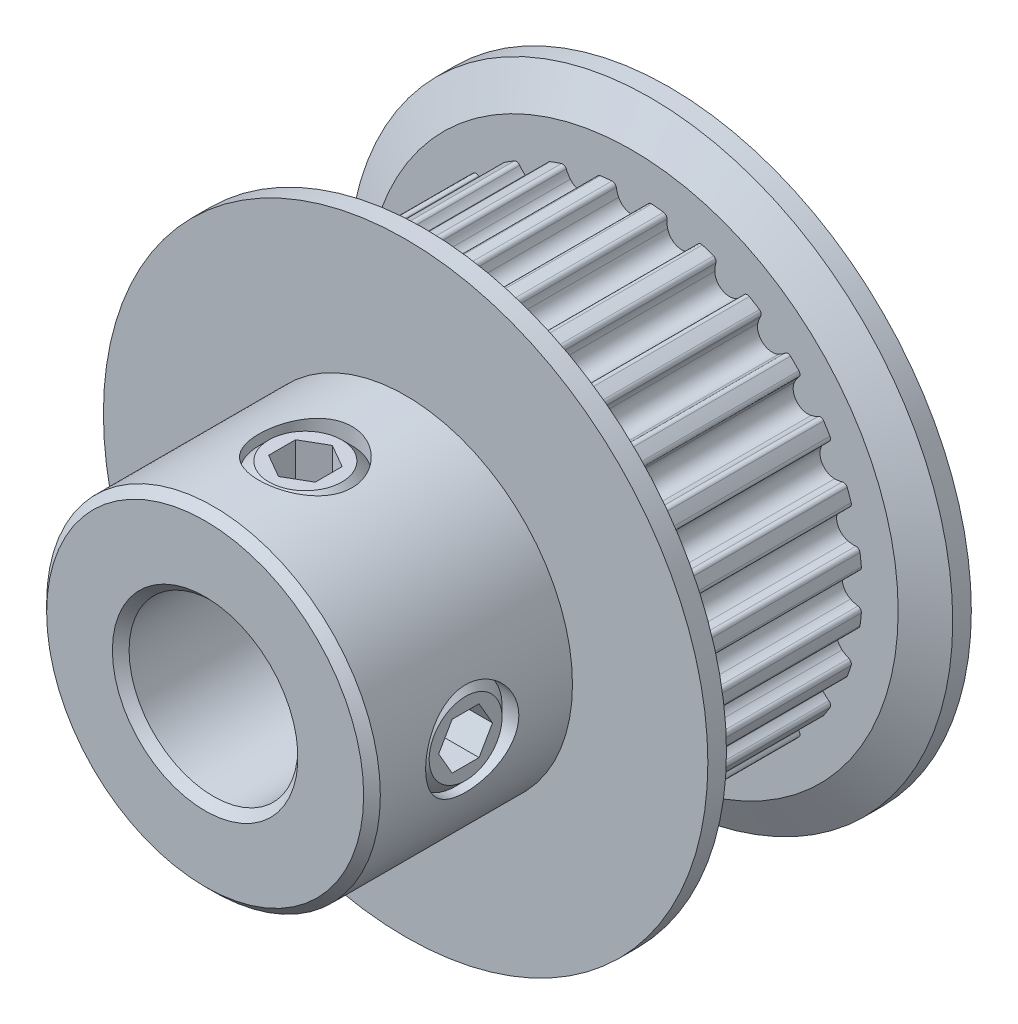
SolidWorks part; units mm, degrees
ref_plane "Front Plane" through (0, 0, 0) normal (0, 0, 1) x (1, 0, 0)
ref_plane "Top Plane" through (0, 0, 0) normal (0, 1, 0) x (1, 0, 0)
ref_plane "Right Plane" through (0, 0, 0) normal (1, 0, 0) x (0, 0, -1)
sketch "Sketch1" plane through (0, 0, 0) normal (0, 0, 1) x (1, 0, 0)
  line L1 (-1.8091, 7.9115) -> (1.8091, 7.9115) construction
  line L4 (0, 0) -> (0, 7.9115) construction
  line L5 (0, 7.9115) -> (0, 12.1188) construction
  line L6 (0, 8.9155) -> (1.9874, 8.6912) construction
  line L7 (1.9874, 8.6912) -> (2.7671, 8.5129) construction
  line L8 (1.9874, 8.6912) -> (1.8091, 7.9115) construction
  line L9 (-1.9874, 8.6912) -> (-1.8091, 7.9115) construction
  line L10 (-1.9308, 8.4436) -> (-2.5991, 11.3665)
  line L11 (-2.5991, 11.3665) -> (2.5991, 11.3665)
  line L12 (2.5991, 11.3665) -> (1.9308, 8.4436)
  circle A0 centre (0, 0) radius 8.9155 construction
  circle A1 centre (0, 0) radius 11.3665 construction
  circle A2 centre (0, 0) radius 8.6615 construction
  arc A3 (-0.4989, 8.2233) -> (0.4989, 8.2233) centre (0, 8.4665) ccw
  arc A4 (-0.4989, 8.2233) -> (-0.5874, 8.5034) centre (0.4, 8.6615) cw
  arc A5 (-1.9308, 8.4436) -> (-0.7485, 8.6291) centre (0, 0) cw
  arc A6 (-0.5874, 8.5034) -> (-0.7485, 8.6291) centre (-0.7355, 8.4797) ccw
  arc A7 (1.9308, 8.4436) -> (0.7485, 8.6291) centre (0, 0) ccw
  arc A8 (0.5874, 8.5034) -> (0.7485, 8.6291) centre (0.7355, 8.4797) cw
  arc A9 (0.4989, 8.2233) -> (0.5874, 8.5034) centre (-0.4, 8.6615) ccw
  point P6 (0, 20.9083)
  point P11 (0, 8.9155)
  point P13 (0, 11.3665)
  point P14 (0, 8.6615)
  dimension "D1" = 8.7896
  dimension "D2" = 3.2033
sketch "Sketch2" plane through (0, 0, 0) normal (1, 0, 0) x (0, 0, -1)
  line L0 (-8.7249, 3.175) -> (8.7249, 3.175)
  line L1 (-8.7249, 3.175) -> (-8.7249, 6.275)
  line L2 (-8.7249, 6.275) -> (-1.1851, 6.275)
  line L3 (-1.1851, 6.275) -> (-1.1851, 11.3665)
  line L4 (-1.1851, 11.3665) -> (0.2149, 11.3665) construction
  line L5 (0.2149, 11.3665) -> (0.2149, 8.6615) construction
  line L6 (0.2149, 8.6615) -> (7.3249, 8.6615)
  line L7 (7.3249, 8.6615) -> (7.3249, 11.3665) construction
  line L8 (7.3249, 11.3665) -> (8.7249, 11.3665) construction
  line L9 (8.7249, 11.3665) -> (8.7249, 3.175)
  line L10 (-8.7249, 0) -> (8.7249, 0) construction
  line L11 (8.0249, 11.3665) -> (7.3249, 10.014)
  line L12 (0.2149, 10.014) -> (-0.4851, 11.3665)
  line L13 (-1.1851, 11.3665) -> (-0.4851, 11.3665)
  line L14 (0.2149, 10.014) -> (0.2149, 8.6615)
  line L15 (7.3249, 8.6615) -> (7.3249, 10.014)
  line L16 (8.0249, 11.3665) -> (8.7249, 11.3665)
  arc A0 (0.2149, 10.014) -> (-0.4851, 11.3665) centre (-1.4417, 10.014) ccw construction
  arc A1 (7.3249, 10.014) -> (8.0249, 11.3665) centre (8.9815, 10.014) cw construction
  point P12 (0.2149, 10.014)
  point P14 (-0.4851, 11.3665)
  point P20 (7.3249, 10.014)
  point P21 (8.0249, 11.3665)
  point P25 (7.3249, 0)
  point P26 (0.2149, 0)
revolve "Revolve1" add sketch "Sketch2" angle 360 mid plane about L10
sketch "Sketch3" plane through (0, 0, 0) normal (0, 0, 1) x (1, 0, 0)
  line L6 (2.5991, 11.3665) -> (-2.5991, 11.3665)
  line L7 (1.9308, 8.4436) -> (2.5991, 11.3665)
  line L8 (-2.5991, 11.3665) -> (-1.9308, 8.4436)
  line L9 (2.5991, 11.3665) -> (-2.5991, 11.3665)
  line L10 (1.9308, 8.4436) -> (2.5991, 11.3665)
  line L11 (-2.5991, 11.3665) -> (-1.9308, 8.4436)
  arc A8 (1.9308, 8.4436) -> (0.7485, 8.6291) centre (0, 0) ccw
  arc A9 (0.7485, 8.6291) -> (0.5874, 8.5034) centre (0.7355, 8.4797) ccw
  arc A10 (0.4989, 8.2233) -> (0.5874, 8.5034) centre (-0.4, 8.6615) ccw
  arc A11 (-0.4989, 8.2233) -> (0.4989, 8.2233) centre (0, 8.4665) ccw
  arc A12 (-0.5874, 8.5034) -> (-0.4989, 8.2233) centre (0.4, 8.6615) ccw
  arc A13 (-0.5874, 8.5034) -> (-0.7485, 8.6291) centre (-0.7355, 8.4797) ccw
  arc A14 (-0.7485, 8.6291) -> (-1.9308, 8.4436) centre (0, 0) ccw
  arc A15 (1.9308, 8.4436) -> (0.7485, 8.6291) centre (0, 0) ccw
  arc A16 (0.7485, 8.6291) -> (0.5874, 8.5034) centre (0.7355, 8.4797) ccw
  arc A17 (0.4989, 8.2233) -> (0.5874, 8.5034) centre (-0.4, 8.6615) ccw
  arc A18 (-0.4989, 8.2233) -> (0.4989, 8.2233) centre (0, 8.4665) ccw
  arc A19 (-0.5874, 8.5034) -> (-0.4989, 8.2233) centre (0.4, 8.6615) ccw
  arc A20 (-0.5874, 8.5034) -> (-0.7485, 8.6291) centre (-0.7355, 8.4797) ccw
  arc A21 (-0.7485, 8.6291) -> (-1.9308, 8.4436) centre (0, 0) ccw
  dimension "D1" = 0
extrude "Cut-Extrude1" cut sketch "Sketch3" against normal up to vertex (7.3249 mm away) from vertex up to point (0, 8.6615, -7.3249) starting at point (0, 8.6615, -0.2149)
pattern_circular "CirPattern1" count 28 over 360 about axis through (0, 0, 8.7249) along (0, 0, 1) of "Cut-Extrude1"
sketch "Sketch4" plane through (0, 0, 0) normal (1, 0, 0) x (0, -1, 0)
  line L0 (0, -1.1851) -> (0, -8.7249) construction
  line L1 (-6.275, -1.1851) -> (6.275, -1.1851) construction
  line L2 (-6.275, -8.7249) -> (6.275, -8.7249) construction
  circle A0 centre (0, -4.955) radius 1.7526
extrude "Cut-Extrude2" cut sketch "Sketch4" along normal through all
ref_plane "Plane1" through (0, 0, 4.955) normal (0, 0, 1) x (1, 0, 0)
sketch "Sketch5" plane through (0, 0, 4.955) normal (0, 0, 1) x (1, 0, 0)
  line L0 (0, 0.1664) -> (0, 6.275) construction
  line L1 (3.175, -1.3716) -> (3.175, 0)
  line L2 (3.556, -1.7526) -> (5.6443, -1.7526)
  line L3 (3.175, 0) -> (6.275, 0) construction
  line L4 (3.175, 0) -> (6.0253, 0)
  line L5 (6.0253, 0) -> (6.0253, -1.3716)
  line L6 (3.556, -1.7526) -> (3.175, -1.3716)
  line L7 (6.0253, -1.3716) -> (5.6443, -1.7526)
  circle A0 centre (0, 0) radius 6.275 construction
  circle A1 centre (0, 0) radius 3.175 construction
  point P2 (3.175, -1.7526)
  point P11 (6.0253, -1.7526)
revolve "Revolve2" add sketch "Sketch5" angle 360 mid plane about L4
sketch "Sketch6" plane through (6.0253, 5.3841, 0) normal (-1, 0, 0) x (0, -1, 0)
  line L1 (5.3841, 5.9669) -> (4.5078, 5.4609)
  line L2 (4.5078, 5.4609) -> (4.5078, 4.4491)
  line L3 (4.5078, 4.4491) -> (5.3841, 3.9431)
  line L4 (5.3841, 3.9431) -> (6.2604, 4.4491)
  line L5 (6.2604, 4.4491) -> (6.2604, 5.4609)
  line L6 (6.2604, 5.4609) -> (5.3841, 5.9669)
  circle A0 centre (5.3841, 4.955) radius 0.8763 construction
  dimension "D1" = 1.7526
extrude "Cut-Extrude3" cut sketch "Sketch6" along normal blind 1.3144
pattern_circular "CirPattern2" count 2 over 90 about axis through (0, 0, 8.7249) along (0, 0, 1) of "Cut-Extrude2", "Revolve2", "Cut-Extrude3"
chamfer "Chamfer1" distance 0.3138 angle 45 2 edges at (3.175, 0, 8.7249) (6.275, 0, 8.7249)
ref_axis "Center Axis 1" through (0, 0, -8.7249) along (0, 0, 1)
ref_plane "Contact Plane 1" through (0, 0, 8.7249) normal (0, 0, 1) x (1, 0, 0)
ref_plane "Contact Plane 2" through (0, 0, -8.7249) normal (0, 0, -1) x (-1, 0, 0)
equation "\"D2@Sketch1\" = \"D1@Sketch1\"/2"
equation "\"D1@Sketch6\" = \"Set Screw@Sketch4\" / 2"
equation "\"D1@Cut-Extrude3\" = \"D1@Sketch6\"*.75"
equation "\"D1@Chamfer1\"=\"Hub Dia@Sketch2\"*.025"
